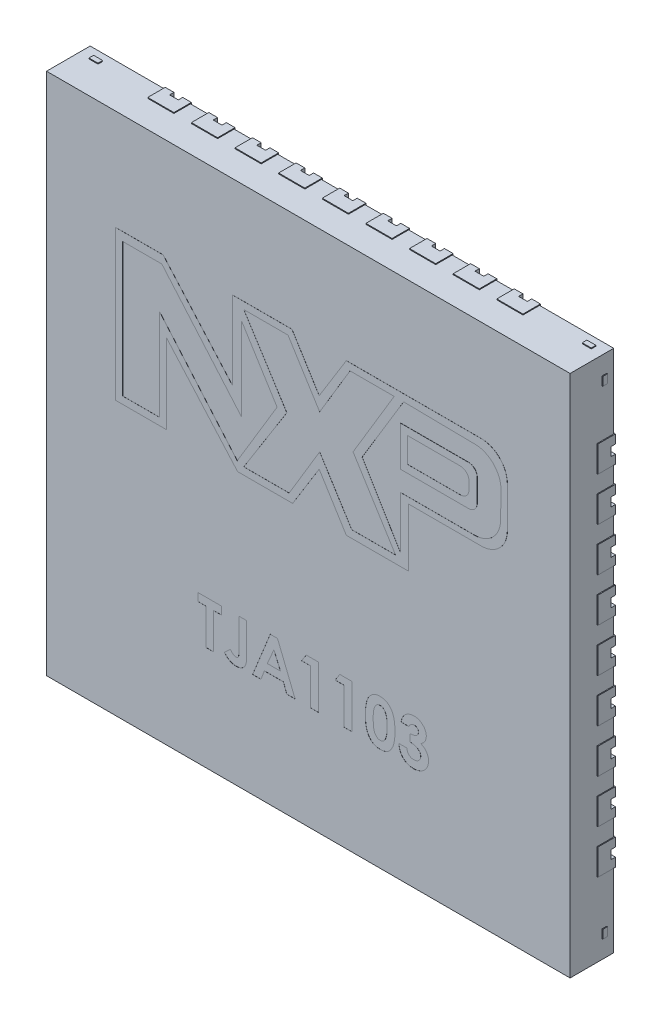
SolidWorks part; units mm, degrees
ref_plane "Front Plane" through (0, 0, 0) normal (0, 0, 1) x (1, 0, 0)
ref_plane "Top Plane" through (0, 0, 0) normal (0, 1, 0) x (1, 0, 0)
ref_plane "Right Plane" through (0, 0, 0) normal (1, 0, 0) x (0, 0, -1)
sketch "Sketch1" plane through (0, 0, 0) normal (0, 0, 1) x (1, 0, 0)
  line L1 (3, -3) -> (-3, -3)
  line L2 (3, -3) -> (3, 3)
  line L3 (3, 3) -> (-3, 3)
  line L4 (-3, -3) -> (-3, 3)
  line L5 (3, -3) -> (-3, 3) construction
  line L6 (3, 3) -> (-3, -3) construction
  point P0 (0, 0)
  dimension "D1" = 6
  dimension "D2" = 6
extrude "Boss-Extrude1" add sketch "Sketch1" along normal blind 0.5
sketch "Sketch3" plane through (0, 0, 0.5) normal (0, 0, 1) x (1, 0, 0)
  line L1 (-1.8824, 1.9808) -> (1.8824, 1.9808)
  line L2 (-1.8824, 1.9808) -> (-1.8824, -1.9808)
  line L3 (-1.8824, -1.9808) -> (1.8824, -1.9808)
  line L4 (1.8824, 1.9808) -> (1.8824, -1.9808)
  line L5 (-1.8824, 1.9808) -> (1.8824, -1.9808) construction
  line L6 (-1.8824, -1.9808) -> (1.8824, 1.9808) construction
  point P0 (0, 0)
sketch "Sketch4" plane through (0, 0, 0) normal (0, 0, -1) x (-1, 0, 0)
  line L0 (1.8824, 1.9808) -> (-1.8824, 1.9808) construction
  line L1 (-1.6324, 1.9808) -> (1.6324, 1.9808)
  line L2 (-1.8824, 1.7308) -> (-1.8824, -1.7308)
  line L3 (-1.6324, -1.9808) -> (1.6324, -1.9808)
  line L5 (-1.8824, 1.9808) -> (1.8824, -1.9808) construction
  line L6 (-1.8824, -1.9808) -> (1.8824, 1.9808) construction
  line L7 (-1.8824, 1.9808) -> (-1.8824, -1.9808) construction
  line L8 (1.8824, 1.7308) -> (1.8824, 1.4732)
  line L9 (1.8824, 1.9808) -> (1.8824, -1.9808) construction
  line L10 (1.8824, 0.8432) -> (1.8824, -1.7308)
  arc A0 (1.6324, -1.9808) -> (1.8824, -1.7308) centre (1.6324, -1.7308) ccw
  arc A1 (-1.8824, -1.7308) -> (-1.6324, -1.9808) centre (-1.6324, -1.7308) ccw
  arc A2 (1.6324, 1.9808) -> (1.8824, 1.7308) centre (1.6324, 1.7308) cw
  arc A3 (-1.6324, 1.9808) -> (-1.8824, 1.7308) centre (-1.6324, 1.7308) ccw
  arc A4 (1.8127, 1.3779) -> (1.8127, 0.9385) centre (1.8824, 1.1582) ccw
  arc A5 (1.8127, 0.9385) -> (1.8824, 0.8432) centre (1.7824, 0.8432) cw
  arc A6 (1.8824, 1.4732) -> (1.8127, 1.3779) centre (1.7824, 1.4732) cw
  point P0 (0, 0)
  point P29 (1.8824, 0.9277)
  point P32 (1.8824, 1.3887)
  dimension "D3" = 0.25
  dimension "D4" = 0.1
  dimension "D1" = 0
  dimension "D2" = 0
extrude "Cut-Extrude2" cut sketch "Sketch4" against normal blind 0.001
sketch "Sketch6" plane through (0, 0, 0.5) normal (0, 0, 1) x (1, 0, 0)
  line L0 (70.7212, 256.7277) -> (518.7212, 256.7277) construction
  line L1 (-2.2083, 0.1303) -> (-2.2083, 1.8455)
  line L2 (-2.2083, 1.8455) -> (-1.6631, 1.8455)
  line L3 (-1.6631, 1.8455) -> (-0.866, 0.9441)
  line L4 (-0.866, 0.9441) -> (-0.866, 1.8455)
  line L5 (-0.866, 1.8455) -> (-0.1867, 1.8455)
  line L6 (-0.1867, 1.8455) -> (0.1255, 1.3423)
  line L7 (0.1255, 1.3423) -> (0.4363, 1.8455)
  line L8 (0.4363, 1.8455) -> (1.9817, 1.8455)
  line L9 (2.2817, 1.5455) -> (2.2817, 1.0794)
  line L10 (1.9817, 0.7794) -> (1.148, 0.7794)
  line L11 (1.148, 0.7794) -> (1.148, 0.1127)
  line L12 (1.148, 0.1127) -> (0.4363, 0.1127)
  line L13 (0.4363, 0.1127) -> (0.1255, 0.6138)
  line L14 (0.1255, 0.6138) -> (-0.1785, 0.1216)
  line L15 (-0.1785, 0.1216) -> (-0.8093, 0.1216)
  line L16 (-0.8093, 0.1216) -> (-1.6263, 1.0454)
  line L17 (-1.6263, 1.0454) -> (-1.6263, 0.1303)
  line L18 (-1.6263, 0.1303) -> (-2.2083, 0.1303)
  line L19 (-2.1262, 0.213) -> (-2.1262, 1.7478)
  line L20 (-2.1262, 1.7478) -> (-1.6777, 1.7478)
  line L21 (-1.6777, 1.7478) -> (-0.7643, 0.6866)
  line L22 (-0.7643, 0.6866) -> (-0.7643, 1.6405)
  line L23 (-0.7643, 1.6405) -> (-0.3567, 0.9874)
  line L24 (-0.3567, 0.9874) -> (-0.8135, 0.2272)
  line L25 (-0.8135, 0.2272) -> (-1.7039, 1.2616)
  line L26 (-1.7039, 1.2616) -> (-1.7039, 0.213)
  line L27 (-1.7039, 0.213) -> (-2.1262, 0.213)
  line L28 (-0.739, 1.7656) -> (-0.2318, 1.7656)
  line L29 (-0.2318, 1.7656) -> (0.1309, 1.1851)
  line L30 (0.1309, 1.1851) -> (0.4789, 1.7656)
  line L31 (0.4789, 1.7656) -> (0.9852, 1.7656)
  line L32 (0.9852, 1.7656) -> (0.5138, 0.9793)
  line L33 (0.5138, 0.9793) -> (1.0013, 0.1991)
  line L34 (1.0013, 0.1991) -> (0.4983, 0.1991)
  line L35 (0.4983, 0.1991) -> (0.1309, 0.7872)
  line L36 (0.1309, 0.7872) -> (-0.2187, 0.2041)
  line L37 (-0.2187, 0.2041) -> (-0.739, 0.2041)
  line L38 (-0.739, 0.2041) -> (-0.2458, 0.9874)
  line L39 (-0.2458, 0.9874) -> (-0.739, 1.7656)
  line L40 (1.0935, 1.7656) -> (1.9132, 1.7541)
  line L41 (2.209, 1.4499) -> (2.2047, 1.1439)
  line L42 (1.9047, 0.8481) -> (1.0599, 0.8481)
  line L43 (1.0599, 0.8481) -> (1.0599, 0.2452)
  line L44 (1.0599, 0.2452) -> (0.6173, 0.9793)
  line L45 (0.6173, 0.9793) -> (1.0935, 1.7656)
  line L47 (1.0599, 1.5374) -> (1.8371, 1.5374)
  line L48 (1.9371, 1.4374) -> (1.9371, 1.1794)
  line L49 (1.8371, 1.0794) -> (1.0599, 1.0794)
  line L50 (1.0599, 1.5374) -> (1.0599, 1.0794)
  line L51 (1.1403, 1.4544) -> (1.7437, 1.4544)
  line L52 (1.1403, 1.4544) -> (1.1403, 1.1679)
  line L53 (1.1403, 1.1679) -> (1.7437, 1.1679)
  line L54 (1.8437, 1.3544) -> (1.8437, 1.2679)
  arc A0 (2.2817, 1.0794) -> (1.9817, 0.7794) centre (1.9817, 1.0794) cw
  arc A1 (1.9817, 1.8455) -> (2.2817, 1.5455) centre (1.9817, 1.5455) cw
  arc A2 (2.2047, 1.1439) -> (1.9047, 0.8481) centre (1.9047, 1.1481) cw
  arc A3 (1.9132, 1.7541) -> (2.209, 1.4499) centre (1.909, 1.4541) cw
  arc A4 (1.7437, 1.1679) -> (1.8437, 1.2679) centre (1.7437, 1.2679) ccw
  arc A5 (1.7437, 1.4544) -> (1.8437, 1.3544) centre (1.7437, 1.3544) cw
  arc A6 (1.9371, 1.1794) -> (1.8371, 1.0794) centre (1.8371, 1.1794) cw
  arc A7 (1.8371, 1.5374) -> (1.9371, 1.4374) centre (1.8371, 1.4374) cw
  dimension "D1" = 0.3
  dimension "D2" = 0.3
  dimension "D3" = 0.1
extrude "Boss-Extrude2" add sketch "Sketch6" along normal blind 0.001 contours A1 L8 L7 L6 L5 L4 L3 L2 L1 L18 L17 L16 L15 L14 L13 L12 L11 L10 A0 L9 L38 L39 L28 L29 L30 L31 L32 L33 L34 L35 L36 L37 L26 L27 L19 L20 L21 L22 L23 L24 L25 L40 A3 L41 A2 L42 L43 L44 | L52 L51 A5 L54 A4 L53 region at (-2.1602, 0.9879, 0.5)
sketch "Sketch8" plane through (0, 0, 0.5) normal (0, 0, 1) x (1, 0, 0)
  line L0 (-1.2697, -1.8064) -> (2.0877, -1.8064) construction
  text T0 "<b>TJA1103</b>" font "Century Gothic" height 0.5
  point P3 (-1.2346, -1.7332)
  point P4 (-1.5512, -1.7332)
  point P5 (-1.4079, -1.7332)
  point P6 (-1.2044, -1.7785)
  point P7 (0, 0)
  point P8 (-1.2697, -1.8064)
extrude "Cut-Extrude3" cut sketch "Sketch8" against normal blind 0.001
sketch "Sketch2" plane through (0, 0, 0) normal (0, 0, -1) x (-1, 0, 0)
  line L0 (-2, 2.65) -> (-2, 3.35) construction
  line L1 (-2.15, 2.65) -> (-2.15, 3.35)
  line L2 (-1.85, 2.65) -> (-1.85, 3.35)
  line L3 (-1.35, 2.65) -> (-1.35, 3.35)
  line L6 (-3, 3) -> (3, 3) construction
  line L7 (-1.65, 2.65) -> (-1.65, 3.35)
  line L8 (-1.5, 2.65) -> (-1.5, 3.35) construction
  line L9 (-0.85, 2.65) -> (-0.85, 3.35)
  line L10 (-1.15, 2.65) -> (-1.15, 3.35)
  line L11 (-1, 2.65) -> (-1, 3.35) construction
  line L12 (-0.35, 2.65) -> (-0.35, 3.35)
  line L13 (-0.65, 2.65) -> (-0.65, 3.35)
  line L14 (-0.5, 2.65) -> (-0.5, 3.35) construction
  line L15 (0.15, 2.65) -> (0.15, 3.35)
  line L16 (-0.15, 2.65) -> (-0.15, 3.35)
  line L17 (0, 2.65) -> (0, 3.35) construction
  line L18 (0.65, 2.65) -> (0.65, 3.35)
  line L19 (0.35, 2.65) -> (0.35, 3.35)
  line L20 (0.5, 2.65) -> (0.5, 3.35) construction
  line L21 (1.15, 2.65) -> (1.15, 3.35)
  line L22 (0.85, 2.65) -> (0.85, 3.35)
  line L23 (1, 2.65) -> (1, 3.35) construction
  line L24 (1.65, 2.65) -> (1.65, 3.35)
  line L25 (1.35, 2.65) -> (1.35, 3.35)
  line L26 (1.5, 2.65) -> (1.5, 3.35) construction
  line L27 (2.15, 2.65) -> (2.15, 3.35)
  line L28 (1.85, 2.65) -> (1.85, 3.35)
  line L29 (2, 2.65) -> (2, 3.35) construction
  line L30 (0, 0) -> (0, -1.6259) construction
  line L31 (0, 0) -> (1.65, 0) construction
  line L32 (-2, -2.65) -> (-2, -3.35) construction
  line L33 (-2.15, -2.65) -> (-2.15, -3.35)
  line L34 (-1.85, -2.65) -> (-1.85, -3.35)
  line L35 (-1.5, -2.65) -> (-1.5, -3.35) construction
  line L36 (-1.65, -2.65) -> (-1.65, -3.35)
  line L37 (-1.35, -2.65) -> (-1.35, -3.35)
  line L38 (-1, -2.65) -> (-1, -3.35) construction
  line L39 (-1.15, -2.65) -> (-1.15, -3.35)
  line L40 (-0.85, -2.65) -> (-0.85, -3.35)
  line L41 (-0.5, -2.65) -> (-0.5, -3.35) construction
  line L42 (-0.65, -2.65) -> (-0.65, -3.35)
  line L43 (-0.35, -2.65) -> (-0.35, -3.35)
  line L44 (0, -2.65) -> (0, -3.35) construction
  line L45 (-0.15, -2.65) -> (-0.15, -3.35)
  line L46 (0.15, -2.65) -> (0.15, -3.35)
  line L47 (0.5, -2.65) -> (0.5, -3.35) construction
  line L48 (0.35, -2.65) -> (0.35, -3.35)
  line L49 (0.65, -2.65) -> (0.65, -3.35)
  line L50 (1, -2.65) -> (1, -3.35) construction
  line L51 (0.85, -2.65) -> (0.85, -3.35)
  line L52 (1.15, -2.65) -> (1.15, -3.35)
  line L53 (1.5, -2.65) -> (1.5, -3.35) construction
  line L54 (1.35, -2.65) -> (1.35, -3.35)
  line L55 (1.65, -2.65) -> (1.65, -3.35)
  line L56 (2, -2.65) -> (2, -3.35) construction
  line L57 (1.85, -2.65) -> (1.85, -3.35)
  line L58 (2.15, -2.65) -> (2.15, -3.35)
  line L59 (2.65, 2) -> (3.35, 2) construction
  line L61 (-2.65, 2) -> (-3.35, 2) construction
  line L62 (-2.65, 2.15) -> (-3.35, 2.15)
  line L63 (-2.65, 1.85) -> (-3.35, 1.85)
  line L64 (-2.65, 1.5) -> (-3.35, 1.5) construction
  line L65 (-2.65, 1.65) -> (-3.35, 1.65)
  line L66 (-2.65, 1.35) -> (-3.35, 1.35)
  line L67 (-2.65, 1) -> (-3.35, 1) construction
  line L68 (-2.65, 1.15) -> (-3.35, 1.15)
  line L69 (-2.65, 0.85) -> (-3.35, 0.85)
  line L70 (-2.65, 0.5) -> (-3.35, 0.5) construction
  line L71 (-2.65, 0.65) -> (-3.35, 0.65)
  line L72 (-2.65, 0.35) -> (-3.35, 0.35)
  line L73 (-2.65, 0) -> (-3.35, 0) construction
  line L74 (-2.65, 0.15) -> (-3.35, 0.15)
  line L75 (-2.65, -0.15) -> (-3.35, -0.15)
  line L76 (-2.65, -0.5) -> (-3.35, -0.5) construction
  line L77 (-2.65, -0.35) -> (-3.35, -0.35)
  line L78 (-2.65, -0.65) -> (-3.35, -0.65)
  line L79 (-2.65, -1) -> (-3.35, -1) construction
  line L80 (-2.65, -0.85) -> (-3.35, -0.85)
  line L81 (-2.65, -1.15) -> (-3.35, -1.15)
  line L82 (-2.65, -1.5) -> (-3.35, -1.5) construction
  line L83 (-2.65, -1.35) -> (-3.35, -1.35)
  line L84 (-2.65, -1.65) -> (-3.35, -1.65)
  line L85 (-2.65, -2) -> (-3.35, -2) construction
  line L86 (-2.65, -1.85) -> (-3.35, -1.85)
  line L87 (-2.65, -2.15) -> (-3.35, -2.15)
  line L88 (2.65, 2.15) -> (3.35, 2.15)
  line L89 (2.65, 1.85) -> (3.35, 1.85)
  line L90 (2.65, 1.5) -> (3.35, 1.5) construction
  line L91 (2.65, 1.65) -> (3.35, 1.65)
  line L92 (2.65, 1.35) -> (3.35, 1.35)
  line L93 (2.65, 1) -> (3.35, 1) construction
  line L94 (2.65, 1.15) -> (3.35, 1.15)
  line L95 (2.65, 0.85) -> (3.35, 0.85)
  line L96 (2.65, 0.5) -> (3.35, 0.5) construction
  line L97 (2.65, 0.65) -> (3.35, 0.65)
  line L98 (2.65, 0.35) -> (3.35, 0.35)
  line L99 (2.65, 0) -> (3.35, 0) construction
  line L100 (2.65, 0.15) -> (3.35, 0.15)
  line L101 (2.65, -0.15) -> (3.35, -0.15)
  line L102 (2.65, -0.5) -> (3.35, -0.5) construction
  line L103 (2.65, -0.35) -> (3.35, -0.35)
  line L104 (2.65, -0.65) -> (3.35, -0.65)
  line L105 (2.65, -1) -> (3.35, -1) construction
  line L106 (2.65, -0.85) -> (3.35, -0.85)
  line L107 (2.65, -1.15) -> (3.35, -1.15)
  line L108 (2.65, -1.5) -> (3.35, -1.5) construction
  line L109 (2.65, -1.35) -> (3.35, -1.35)
  line L110 (2.65, -1.65) -> (3.35, -1.65)
  line L111 (2.65, -2) -> (3.35, -2) construction
  line L112 (2.65, -1.85) -> (3.35, -1.85)
  line L113 (2.65, -2.15) -> (3.35, -2.15)
  arc A0 (-2.15, 2.65) -> (-1.85, 2.65) centre (-2, 2.65) ccw
  arc A1 (-1.85, 3.35) -> (-2.15, 3.35) centre (-2, 3.35) ccw
  arc A4 (-1.65, 2.65) -> (-1.35, 2.65) centre (-1.5, 2.65) ccw
  arc A5 (-1.35, 3.35) -> (-1.65, 3.35) centre (-1.5, 3.35) ccw
  arc A6 (-1.15, 2.65) -> (-0.85, 2.65) centre (-1, 2.65) ccw
  arc A7 (-0.85, 3.35) -> (-1.15, 3.35) centre (-1, 3.35) ccw
  arc A8 (-0.65, 2.65) -> (-0.35, 2.65) centre (-0.5, 2.65) ccw
  arc A9 (-0.35, 3.35) -> (-0.65, 3.35) centre (-0.5, 3.35) ccw
  arc A10 (-0.15, 2.65) -> (0.15, 2.65) centre (0, 2.65) ccw
  arc A11 (0.15, 3.35) -> (-0.15, 3.35) centre (0, 3.35) ccw
  arc A12 (0.35, 2.65) -> (0.65, 2.65) centre (0.5, 2.65) ccw
  arc A13 (0.65, 3.35) -> (0.35, 3.35) centre (0.5, 3.35) ccw
  arc A14 (0.85, 2.65) -> (1.15, 2.65) centre (1, 2.65) ccw
  arc A15 (1.15, 3.35) -> (0.85, 3.35) centre (1, 3.35) ccw
  arc A16 (1.35, 2.65) -> (1.65, 2.65) centre (1.5, 2.65) ccw
  arc A17 (1.65, 3.35) -> (1.35, 3.35) centre (1.5, 3.35) ccw
  arc A18 (1.85, 2.65) -> (2.15, 2.65) centre (2, 2.65) ccw
  arc A19 (2.15, 3.35) -> (1.85, 3.35) centre (2, 3.35) ccw
  arc A20 (-2.15, -2.65) -> (-1.85, -2.65) centre (-2, -2.65) cw
  arc A21 (-1.85, -3.35) -> (-2.15, -3.35) centre (-2, -3.35) cw
  arc A22 (-1.65, -2.65) -> (-1.35, -2.65) centre (-1.5, -2.65) cw
  arc A23 (-1.35, -3.35) -> (-1.65, -3.35) centre (-1.5, -3.35) cw
  arc A24 (-1.15, -2.65) -> (-0.85, -2.65) centre (-1, -2.65) cw
  arc A25 (-0.85, -3.35) -> (-1.15, -3.35) centre (-1, -3.35) cw
  arc A26 (-0.65, -2.65) -> (-0.35, -2.65) centre (-0.5, -2.65) cw
  arc A27 (-0.35, -3.35) -> (-0.65, -3.35) centre (-0.5, -3.35) cw
  arc A28 (-0.15, -2.65) -> (0.15, -2.65) centre (0, -2.65) cw
  arc A29 (0.15, -3.35) -> (-0.15, -3.35) centre (0, -3.35) cw
  arc A30 (0.35, -2.65) -> (0.65, -2.65) centre (0.5, -2.65) cw
  arc A31 (0.65, -3.35) -> (0.35, -3.35) centre (0.5, -3.35) cw
  arc A32 (0.85, -2.65) -> (1.15, -2.65) centre (1, -2.65) cw
  arc A33 (1.15, -3.35) -> (0.85, -3.35) centre (1, -3.35) cw
  arc A34 (1.35, -2.65) -> (1.65, -2.65) centre (1.5, -2.65) cw
  arc A35 (1.65, -3.35) -> (1.35, -3.35) centre (1.5, -3.35) cw
  arc A36 (1.85, -2.65) -> (2.15, -2.65) centre (2, -2.65) cw
  arc A37 (2.15, -3.35) -> (1.85, -3.35) centre (2, -3.35) cw
  arc A38 (-2.65, 2.15) -> (-2.65, 1.85) centre (-2.65, 2) cw
  arc A39 (-3.35, 1.85) -> (-3.35, 2.15) centre (-3.35, 2) cw
  arc A40 (-2.65, 1.65) -> (-2.65, 1.35) centre (-2.65, 1.5) cw
  arc A41 (-3.35, 1.35) -> (-3.35, 1.65) centre (-3.35, 1.5) cw
  arc A42 (-2.65, 1.15) -> (-2.65, 0.85) centre (-2.65, 1) cw
  arc A43 (-3.35, 0.85) -> (-3.35, 1.15) centre (-3.35, 1) cw
  arc A44 (-2.65, 0.65) -> (-2.65, 0.35) centre (-2.65, 0.5) cw
  arc A45 (-3.35, 0.35) -> (-3.35, 0.65) centre (-3.35, 0.5) cw
  arc A46 (-2.65, 0.15) -> (-2.65, -0.15) centre (-2.65, 0) cw
  arc A47 (-3.35, -0.15) -> (-3.35, 0.15) centre (-3.35, 0) cw
  arc A48 (-2.65, -0.35) -> (-2.65, -0.65) centre (-2.65, -0.5) cw
  arc A49 (-3.35, -0.65) -> (-3.35, -0.35) centre (-3.35, -0.5) cw
  arc A50 (-2.65, -0.85) -> (-2.65, -1.15) centre (-2.65, -1) cw
  arc A51 (-3.35, -1.15) -> (-3.35, -0.85) centre (-3.35, -1) cw
  arc A52 (-2.65, -1.35) -> (-2.65, -1.65) centre (-2.65, -1.5) cw
  arc A53 (-3.35, -1.65) -> (-3.35, -1.35) centre (-3.35, -1.5) cw
  arc A54 (-2.65, -1.85) -> (-2.65, -2.15) centre (-2.65, -2) cw
  arc A55 (-3.35, -2.15) -> (-3.35, -1.85) centre (-3.35, -2) cw
  arc A56 (2.65, 2.15) -> (2.65, 1.85) centre (2.65, 2) ccw
  arc A57 (3.35, 1.85) -> (3.35, 2.15) centre (3.35, 2) ccw
  arc A58 (2.65, 1.65) -> (2.65, 1.35) centre (2.65, 1.5) ccw
  arc A59 (3.35, 1.35) -> (3.35, 1.65) centre (3.35, 1.5) ccw
  arc A60 (2.65, 1.15) -> (2.65, 0.85) centre (2.65, 1) ccw
  arc A61 (3.35, 0.85) -> (3.35, 1.15) centre (3.35, 1) ccw
  arc A62 (2.65, 0.65) -> (2.65, 0.35) centre (2.65, 0.5) ccw
  arc A63 (3.35, 0.35) -> (3.35, 0.65) centre (3.35, 0.5) ccw
  arc A64 (2.65, 0.15) -> (2.65, -0.15) centre (2.65, 0) ccw
  arc A65 (3.35, -0.15) -> (3.35, 0.15) centre (3.35, 0) ccw
  arc A66 (2.65, -0.35) -> (2.65, -0.65) centre (2.65, -0.5) ccw
  arc A67 (3.35, -0.65) -> (3.35, -0.35) centre (3.35, -0.5) ccw
  arc A68 (2.65, -0.85) -> (2.65, -1.15) centre (2.65, -1) ccw
  arc A69 (3.35, -1.15) -> (3.35, -0.85) centre (3.35, -1) ccw
  arc A70 (2.65, -1.35) -> (2.65, -1.65) centre (2.65, -1.5) ccw
  arc A71 (3.35, -1.65) -> (3.35, -1.35) centre (3.35, -1.5) ccw
  arc A72 (2.65, -1.85) -> (2.65, -2.15) centre (2.65, -2) ccw
  arc A73 (3.35, -2.15) -> (3.35, -1.85) centre (3.35, -2) ccw
  point P2 (-2, 3)
  point P10 (-1.5, 3)
  point P16 (-2, 2.5)
  point P21 (-1, 3)
  point P28 (-0.5, 3)
  point P35 (0, 3)
  point P42 (0.5, 3)
  point P49 (1, 3)
  point P56 (1.5, 3)
  point P63 (2, 3)
  point P72 (-2, -3)
  point P79 (-1.5, -3)
  point P86 (-1, -3)
  point P93 (-0.5, -3)
  point P100 (0, -3)
  point P107 (0.5, -3)
  point P114 (1, -3)
  point P121 (1.5, -3)
  point P128 (2, -3)
  point P136 (3, 2)
  point P140 (-3, 2)
  point P147 (-3, 1.5)
  point P154 (-3, 1)
  point P161 (-3, 0.5)
  point P168 (-3, 0)
  point P175 (-3, -0.5)
  point P182 (-3, -1)
  point P189 (-3, -1.5)
  point P196 (-3, -2)
  point P206 (3, 1.5)
  point P213 (3, 1)
  point P220 (3, 0.5)
  point P227 (3, 0)
  point P234 (3, -0.5)
  point P241 (3, -1)
  point P248 (3, -1.5)
  point P255 (3, -2)
  dimension "D1" = 0.3
  dimension "D2" = 9
  dimension "D4" = 0
  dimension "D5" = 0.5
  dimension "D8" = 2
sketch "Sketch10" plane through (0, 0, 0.5) normal (0, 0, 1) x (1, 0, 0)
  line L0 (1.0599, 1.5374) -> (1.8371, 1.5374)
  line L1 (1.0599, 1.5374) -> (1.0599, 1.0794)
  line L2 (1.0599, 1.0794) -> (1.8371, 1.0794)
  line L3 (1.9371, 1.4374) -> (1.9371, 1.1794)
  line L4 (1.8437, 1.3544) -> (1.8437, 1.2679)
  line L5 (1.7437, 1.4544) -> (1.1403, 1.4544)
  line L6 (1.1403, 1.4544) -> (1.1403, 1.1679)
  line L7 (1.1403, 1.1679) -> (1.7437, 1.1679)
  line L8 (1.1403, 1.4544) -> (1.7437, 1.4544) construction
  line L9 (1.1403, 1.4544) -> (1.1403, 1.1679) construction
  arc A0 (1.8371, 1.5374) -> (1.9371, 1.4374) centre (1.8371, 1.4374) cw
  arc A1 (1.9371, 1.1794) -> (1.8371, 1.0794) centre (1.8371, 1.1794) cw
  arc A2 (1.8437, 1.2679) -> (1.7437, 1.1679) centre (1.7437, 1.2679) cw
  arc A3 (1.7437, 1.4544) -> (1.8437, 1.3544) centre (1.7437, 1.3544) cw
  point P26 (1.0409, 1.4852)
extrude "Boss-Extrude3" add sketch "Sketch10" along normal blind 0.002
extrude "Boss-Extrude4" add sketch "Sketch2" along normal blind 0.01
sketch "Sketch11" plane through (0, 0, 0.5) normal (0, 0, 1) x (1, 0, 0)
  line L1 (-3, 3) -> (3, 3)
  line L2 (-3, 3) -> (-3, -3)
  line L3 (-3, -3) -> (3, -3)
  line L4 (3, 3) -> (3, -3)
  line L5 (-4.69, 4.3097) -> (4.6689, 4.3097)
  line L6 (-4.69, 4.3097) -> (-4.69, -5.1125)
  line L7 (-4.69, -5.1125) -> (4.6689, -5.1125)
  line L8 (4.6689, 4.3097) -> (4.6689, -5.1125)
extrude "Cut-Extrude4" cut sketch "Sketch11" against normal blind 10.01
sketch "Sketch12" plane through (0, 0, -0.01) normal (0, 0, -1) x (-1, 0, 0)
  line L0 (-3, 3) -> (-1.6807, 1.6807) construction
  line L1 (-3, 3) -> (-2.15, 3) construction
  line L2 (0, 0) -> (0.5, 0) construction
  line L3 (0, 0) -> (0, 0.8589) construction
  circle A0 centre (-2, 2.65) radius 0.025
  circle A1 centre (-1.5, 2.65) radius 0.025
  circle A2 centre (-1, 2.65) radius 0.025
  circle A3 centre (-0.5, 2.65) radius 0.025
  circle A4 centre (0, 2.65) radius 0.025
  circle A5 centre (0.5, 2.65) radius 0.025
  circle A6 centre (1, 2.65) radius 0.025
  circle A7 centre (1.5, 2.65) radius 0.025
  circle A8 centre (2, 2.65) radius 0.025
  circle A9 centre (-2.65, -2) radius 0.025
  circle A10 centre (-2.65, -1.5) radius 0.025
  circle A11 centre (-2.65, -1) radius 0.025
  circle A12 centre (-2.65, -0.5) radius 0.025
  circle A13 centre (-2.65, 0) radius 0.025
  circle A14 centre (-2.65, 0.5) radius 0.025
  circle A15 centre (-2.65, 1) radius 0.025
  circle A16 centre (-2.65, 1.5) radius 0.025
  circle A17 centre (-2.65, 2) radius 0.025
  circle A18 centre (2, -2.65) radius 0.025
  circle A19 centre (1.5, -2.65) radius 0.025
  circle A20 centre (1, -2.65) radius 0.025
  circle A21 centre (0.5, -2.65) radius 0.025
  circle A22 centre (0, -2.65) radius 0.025
  circle A23 centre (-0.5, -2.65) radius 0.025
  circle A24 centre (-1, -2.65) radius 0.025
  circle A25 centre (-1.5, -2.65) radius 0.025
  circle A26 centre (-2, -2.65) radius 0.025
  circle A27 centre (2.65, 2) radius 0.025
  circle A28 centre (2.65, 1.5) radius 0.025
  circle A29 centre (2.65, 1) radius 0.025
  circle A30 centre (2.65, 0.5) radius 0.025
  circle A31 centre (2.65, 0) radius 0.025
  circle A32 centre (2.65, -0.5) radius 0.025
  circle A33 centre (2.65, -1) radius 0.025
  circle A34 centre (2.65, -1.5) radius 0.025
  circle A35 centre (2.65, -2) radius 0.025
  dimension "D1" = 0.05
  dimension "D3" = 45
  dimension "D2" = 9
sketch "Sketch14" plane through (0, -3, 0) normal (0, -1, 0) x (1, 0, 0)
  line L0 (-1.85, -0.01) -> (-1.85, 0) construction
  line L1 (-2.15, -0.01) -> (-1.85, -0.01)
  line L2 (-2.15, -0.01) -> (-2.15, 0.19)
  line L3 (-2.15, 0.19) -> (-1.85, 0.19)
  line L4 (-1.85, -0.01) -> (-1.85, 0.19)
  line L5 (-1.65, -0.01) -> (-1.65, 0.19)
  line L6 (-1.65, -0.01) -> (-1.35, -0.01)
  line L7 (-1.35, -0.01) -> (-1.35, 0.19)
  line L8 (-1.65, 0.19) -> (-1.35, 0.19)
  line L9 (-1.15, -0.01) -> (-1.15, 0.19)
  line L10 (-1.15, -0.01) -> (-0.85, -0.01)
  line L11 (-0.85, -0.01) -> (-0.85, 0.19)
  line L12 (-1.15, 0.19) -> (-0.85, 0.19)
  line L13 (-0.65, -0.01) -> (-0.65, 0.19)
  line L14 (-0.65, -0.01) -> (-0.35, -0.01)
  line L15 (-0.35, -0.01) -> (-0.35, 0.19)
  line L16 (-0.65, 0.19) -> (-0.35, 0.19)
  line L17 (-0.15, -0.01) -> (-0.15, 0.19)
  line L18 (-0.15, -0.01) -> (0.15, -0.01)
  line L19 (0.15, -0.01) -> (0.15, 0.19)
  line L20 (-0.15, 0.19) -> (0.15, 0.19)
  line L21 (0.35, -0.01) -> (0.35, 0.19)
  line L22 (0.35, -0.01) -> (0.65, -0.01)
  line L23 (0.65, -0.01) -> (0.65, 0.19)
  line L24 (0.35, 0.19) -> (0.65, 0.19)
  line L25 (0.85, -0.01) -> (0.85, 0.19)
  line L26 (0.85, -0.01) -> (1.15, -0.01)
  line L27 (1.15, -0.01) -> (1.15, 0.19)
  line L28 (0.85, 0.19) -> (1.15, 0.19)
  line L29 (1.35, -0.01) -> (1.35, 0.19)
  line L30 (1.35, -0.01) -> (1.65, -0.01)
  line L31 (1.65, -0.01) -> (1.65, 0.19)
  line L32 (1.35, 0.19) -> (1.65, 0.19)
  line L33 (1.85, -0.01) -> (1.85, 0.19)
  line L34 (1.85, -0.01) -> (2.15, -0.01)
  line L35 (2.15, -0.01) -> (2.15, 0.19)
  line L36 (1.85, 0.19) -> (2.15, 0.19)
  dimension "D1" = 0
  dimension "D2" = 0.2
  dimension "D3" = 9
extrude "Boss-Extrude5" add sketch "Sketch14" along normal blind 0.01
sketch "Sketch15" plane through (-3, 0, 0) normal (-1, 0, 0) x (0, 0, 1)
  line L0 (-0.01, -1.65) -> (-0.01, -1.35)
  line L1 (-0.01, -2.15) -> (0.19, -2.15)
  line L2 (-0.01, -2.15) -> (-0.01, -1.85)
  line L3 (-0.01, -1.85) -> (0.19, -1.85)
  line L4 (0.19, -2.15) -> (0.19, -1.85)
  line L5 (-0.01, -1.65) -> (0.19, -1.65)
  line L6 (0.19, -1.65) -> (0.19, -1.35)
  line L7 (-0.01, -1.35) -> (0.19, -1.35)
  line L8 (-0.01, -1.15) -> (-0.01, -0.85)
  line L9 (-0.01, -1.15) -> (0.19, -1.15)
  line L10 (0.19, -1.15) -> (0.19, -0.85)
  line L11 (-0.01, -0.85) -> (0.19, -0.85)
  line L12 (-0.01, -0.65) -> (-0.01, -0.35)
  line L13 (-0.01, -0.65) -> (0.19, -0.65)
  line L14 (0.19, -0.65) -> (0.19, -0.35)
  line L15 (-0.01, -0.35) -> (0.19, -0.35)
  line L16 (-0.01, -0.15) -> (-0.01, 0.15)
  line L17 (-0.01, -0.15) -> (0.19, -0.15)
  line L18 (0.19, -0.15) -> (0.19, 0.15)
  line L19 (-0.01, 0.15) -> (0.19, 0.15)
  line L20 (-0.01, 0.35) -> (-0.01, 0.65)
  line L21 (-0.01, 0.35) -> (0.19, 0.35)
  line L22 (0.19, 0.35) -> (0.19, 0.65)
  line L23 (-0.01, 0.65) -> (0.19, 0.65)
  line L24 (-0.01, 0.85) -> (-0.01, 1.15)
  line L25 (-0.01, 0.85) -> (0.19, 0.85)
  line L26 (0.19, 0.85) -> (0.19, 1.15)
  line L27 (-0.01, 1.15) -> (0.19, 1.15)
  line L28 (-0.01, 1.35) -> (-0.01, 1.65)
  line L29 (-0.01, 1.35) -> (0.19, 1.35)
  line L30 (0.19, 1.35) -> (0.19, 1.65)
  line L31 (-0.01, 1.65) -> (0.19, 1.65)
  line L32 (-0.01, 1.85) -> (-0.01, 2.15)
  line L33 (-0.01, 1.85) -> (0.19, 1.85)
  line L34 (0.19, 1.85) -> (0.19, 2.15)
  line L35 (-0.01, 2.15) -> (0.19, 2.15)
  dimension "D1" = 0
  dimension "D2" = 0.2
  dimension "D3" = 9
extrude "Boss-Extrude6" add sketch "Sketch15" along normal blind 0.01
mirror "Mirror1" about plane through (0, 0, 0) normal (1, 0, 0) of "Boss-Extrude6"
mirror "Mirror2" about plane through (0, 0, 0) normal (0, 1, 0) of "Boss-Extrude5"
sketch "Sketch16" plane through (0, 0, -0.01) normal (0, 0, -1) x (-1, 0, 0)
  line L0 (-2, 3.06) -> (-2, 2.96) construction
  line L1 (-1.85, 3.01) -> (-2.15, 3.01) construction
  line L2 (-1.95, 3.06) -> (-1.95, 2.96)
  line L3 (-2.05, 3.06) -> (-2.05, 2.96)
  line L4 (-1.55, 3.06) -> (-1.55, 2.96)
  line L5 (-1.45, 3.06) -> (-1.45, 2.96)
  line L6 (-1.5, 3.06) -> (-1.5, 2.96) construction
  line L7 (-1.05, 3.06) -> (-1.05, 2.96)
  line L8 (-0.95, 3.06) -> (-0.95, 2.96)
  line L9 (-1, 3.06) -> (-1, 2.96) construction
  line L10 (-0.55, 3.06) -> (-0.55, 2.96)
  line L11 (-0.45, 3.06) -> (-0.45, 2.96)
  line L12 (-0.5, 3.06) -> (-0.5, 2.96) construction
  line L13 (-0.05, 3.06) -> (-0.05, 2.96)
  line L14 (0.05, 3.06) -> (0.05, 2.96)
  line L15 (0, 3.06) -> (0, 2.96) construction
  line L16 (0.45, 3.06) -> (0.45, 2.96)
  line L17 (0.55, 3.06) -> (0.55, 2.96)
  line L18 (0.5, 3.06) -> (0.5, 2.96) construction
  line L19 (0.95, 3.06) -> (0.95, 2.96)
  line L20 (1.05, 3.06) -> (1.05, 2.96)
  line L21 (1, 3.06) -> (1, 2.96) construction
  line L22 (1.45, 3.06) -> (1.45, 2.96)
  line L23 (1.55, 3.06) -> (1.55, 2.96)
  line L24 (1.5, 3.06) -> (1.5, 2.96) construction
  line L25 (1.95, 3.06) -> (1.95, 2.96)
  line L26 (2.05, 3.06) -> (2.05, 2.96)
  line L27 (2, 3.06) -> (2, 2.96) construction
  line L28 (0, 0) -> (0.7795, 0) construction
  line L29 (0, 0) -> (0, 0.8504) construction
  line L30 (-2, -3.06) -> (-2, -2.96) construction
  line L31 (-1.95, -3.06) -> (-1.95, -2.96)
  line L32 (-2.05, -3.06) -> (-2.05, -2.96)
  line L33 (-1.5, -3.06) -> (-1.5, -2.96) construction
  line L34 (-1.45, -3.06) -> (-1.45, -2.96)
  line L35 (-1.55, -3.06) -> (-1.55, -2.96)
  line L36 (-1, -3.06) -> (-1, -2.96) construction
  line L37 (-0.95, -3.06) -> (-0.95, -2.96)
  line L38 (-1.05, -3.06) -> (-1.05, -2.96)
  line L39 (-0.5, -3.06) -> (-0.5, -2.96) construction
  line L40 (-0.45, -3.06) -> (-0.45, -2.96)
  line L41 (-0.55, -3.06) -> (-0.55, -2.96)
  line L42 (0, -3.06) -> (0, -2.96) construction
  line L43 (0.05, -3.06) -> (0.05, -2.96)
  line L44 (-0.05, -3.06) -> (-0.05, -2.96)
  line L45 (0.5, -3.06) -> (0.5, -2.96) construction
  line L46 (0.55, -3.06) -> (0.55, -2.96)
  line L47 (0.45, -3.06) -> (0.45, -2.96)
  line L48 (1, -3.06) -> (1, -2.96) construction
  line L49 (1.05, -3.06) -> (1.05, -2.96)
  line L50 (0.95, -3.06) -> (0.95, -2.96)
  line L51 (1.5, -3.06) -> (1.5, -2.96) construction
  line L52 (1.55, -3.06) -> (1.55, -2.96)
  line L53 (1.45, -3.06) -> (1.45, -2.96)
  line L54 (2, -3.06) -> (2, -2.96) construction
  line L55 (2.05, -3.06) -> (2.05, -2.96)
  line L56 (1.95, -3.06) -> (1.95, -2.96)
  line L57 (-3.06, 2) -> (-2.96, 2) construction
  line L58 (-3.01, 2.15) -> (-3.01, 1.85) construction
  line L59 (-3.06, 2.05) -> (-2.96, 2.05)
  line L60 (-3.06, 1.95) -> (-2.96, 1.95)
  line L61 (-3.06, 1.45) -> (-2.96, 1.45)
  line L62 (-3.06, 1.55) -> (-2.96, 1.55)
  line L63 (-3.06, 1.5) -> (-2.96, 1.5) construction
  line L64 (-3.06, 0.95) -> (-2.96, 0.95)
  line L65 (-3.06, 1.05) -> (-2.96, 1.05)
  line L66 (-3.06, 1) -> (-2.96, 1) construction
  line L67 (-3.06, 0.45) -> (-2.96, 0.45)
  line L68 (-3.06, 0.55) -> (-2.96, 0.55)
  line L69 (-3.06, 0.5) -> (-2.96, 0.5) construction
  line L70 (-3.06, -0.05) -> (-2.96, -0.05)
  line L71 (-3.06, 0.05) -> (-2.96, 0.05)
  line L72 (-3.06, 0) -> (-2.96, 0) construction
  line L73 (-3.06, -0.55) -> (-2.96, -0.55)
  line L74 (-3.06, -0.45) -> (-2.96, -0.45)
  line L75 (-3.06, -0.5) -> (-2.96, -0.5) construction
  line L76 (-3.06, -1.05) -> (-2.96, -1.05)
  line L77 (-3.06, -0.95) -> (-2.96, -0.95)
  line L78 (-3.06, -1) -> (-2.96, -1) construction
  line L79 (-3.06, -1.55) -> (-2.96, -1.55)
  line L80 (-3.06, -1.45) -> (-2.96, -1.45)
  line L81 (-3.06, -1.5) -> (-2.96, -1.5) construction
  line L82 (-3.06, -2.05) -> (-2.96, -2.05)
  line L83 (-3.06, -1.95) -> (-2.96, -1.95)
  line L84 (-3.06, -2) -> (-2.96, -2) construction
  line L85 (3.06, 2) -> (2.96, 2) construction
  line L86 (3.06, 2.05) -> (2.96, 2.05)
  line L87 (3.06, 1.95) -> (2.96, 1.95)
  line L88 (3.06, 1.5) -> (2.96, 1.5) construction
  line L89 (3.06, 1.55) -> (2.96, 1.55)
  line L90 (3.06, 1.45) -> (2.96, 1.45)
  line L91 (3.06, 1) -> (2.96, 1) construction
  line L92 (3.06, 1.05) -> (2.96, 1.05)
  line L93 (3.06, 0.95) -> (2.96, 0.95)
  line L94 (3.06, 0.5) -> (2.96, 0.5) construction
  line L95 (3.06, 0.55) -> (2.96, 0.55)
  line L96 (3.06, 0.45) -> (2.96, 0.45)
  line L97 (3.06, 0) -> (2.96, 0) construction
  line L98 (3.06, 0.05) -> (2.96, 0.05)
  line L99 (3.06, -0.05) -> (2.96, -0.05)
  line L100 (3.06, -0.5) -> (2.96, -0.5) construction
  line L101 (3.06, -0.45) -> (2.96, -0.45)
  line L102 (3.06, -0.55) -> (2.96, -0.55)
  line L103 (3.06, -1) -> (2.96, -1) construction
  line L104 (3.06, -0.95) -> (2.96, -0.95)
  line L105 (3.06, -1.05) -> (2.96, -1.05)
  line L106 (3.06, -1.5) -> (2.96, -1.5) construction
  line L107 (3.06, -1.45) -> (2.96, -1.45)
  line L108 (3.06, -1.55) -> (2.96, -1.55)
  line L109 (3.06, -2) -> (2.96, -2) construction
  line L110 (3.06, -1.95) -> (2.96, -1.95)
  line L111 (3.06, -2.05) -> (2.96, -2.05)
  arc A0 (-1.95, 3.06) -> (-2.05, 3.06) centre (-2, 3.06) ccw
  arc A1 (-2.05, 2.96) -> (-1.95, 2.96) centre (-2, 2.96) ccw
  arc A2 (-1.45, 3.06) -> (-1.55, 3.06) centre (-1.5, 3.06) ccw
  arc A3 (-1.55, 2.96) -> (-1.45, 2.96) centre (-1.5, 2.96) ccw
  arc A4 (-0.95, 3.06) -> (-1.05, 3.06) centre (-1, 3.06) ccw
  arc A5 (-1.05, 2.96) -> (-0.95, 2.96) centre (-1, 2.96) ccw
  arc A6 (-0.45, 3.06) -> (-0.55, 3.06) centre (-0.5, 3.06) ccw
  arc A7 (-0.55, 2.96) -> (-0.45, 2.96) centre (-0.5, 2.96) ccw
  arc A8 (0.05, 3.06) -> (-0.05, 3.06) centre (0, 3.06) ccw
  arc A9 (-0.05, 2.96) -> (0.05, 2.96) centre (0, 2.96) ccw
  arc A10 (0.55, 3.06) -> (0.45, 3.06) centre (0.5, 3.06) ccw
  arc A11 (0.45, 2.96) -> (0.55, 2.96) centre (0.5, 2.96) ccw
  arc A12 (1.05, 3.06) -> (0.95, 3.06) centre (1, 3.06) ccw
  arc A13 (0.95, 2.96) -> (1.05, 2.96) centre (1, 2.96) ccw
  arc A14 (1.55, 3.06) -> (1.45, 3.06) centre (1.5, 3.06) ccw
  arc A15 (1.45, 2.96) -> (1.55, 2.96) centre (1.5, 2.96) ccw
  arc A16 (2.05, 3.06) -> (1.95, 3.06) centre (2, 3.06) ccw
  arc A17 (1.95, 2.96) -> (2.05, 2.96) centre (2, 2.96) ccw
  arc A18 (-1.95, -3.06) -> (-2.05, -3.06) centre (-2, -3.06) cw
  arc A19 (-2.05, -2.96) -> (-1.95, -2.96) centre (-2, -2.96) cw
  arc A20 (-1.45, -3.06) -> (-1.55, -3.06) centre (-1.5, -3.06) cw
  arc A21 (-1.55, -2.96) -> (-1.45, -2.96) centre (-1.5, -2.96) cw
  arc A22 (-0.95, -3.06) -> (-1.05, -3.06) centre (-1, -3.06) cw
  arc A23 (-1.05, -2.96) -> (-0.95, -2.96) centre (-1, -2.96) cw
  arc A24 (-0.45, -3.06) -> (-0.55, -3.06) centre (-0.5, -3.06) cw
  arc A25 (-0.55, -2.96) -> (-0.45, -2.96) centre (-0.5, -2.96) cw
  arc A26 (0.05, -3.06) -> (-0.05, -3.06) centre (0, -3.06) cw
  arc A27 (-0.05, -2.96) -> (0.05, -2.96) centre (0, -2.96) cw
  arc A28 (0.55, -3.06) -> (0.45, -3.06) centre (0.5, -3.06) cw
  arc A29 (0.45, -2.96) -> (0.55, -2.96) centre (0.5, -2.96) cw
  arc A30 (1.05, -3.06) -> (0.95, -3.06) centre (1, -3.06) cw
  arc A31 (0.95, -2.96) -> (1.05, -2.96) centre (1, -2.96) cw
  arc A32 (1.55, -3.06) -> (1.45, -3.06) centre (1.5, -3.06) cw
  arc A33 (1.45, -2.96) -> (1.55, -2.96) centre (1.5, -2.96) cw
  arc A34 (2.05, -3.06) -> (1.95, -3.06) centre (2, -3.06) cw
  arc A35 (1.95, -2.96) -> (2.05, -2.96) centre (2, -2.96) cw
  arc A36 (-3.06, 2.05) -> (-3.06, 1.95) centre (-3.06, 2) ccw
  arc A37 (-2.96, 1.95) -> (-2.96, 2.05) centre (-2.96, 2) ccw
  arc A38 (-3.06, 1.55) -> (-3.06, 1.45) centre (-3.06, 1.5) ccw
  arc A39 (-2.96, 1.45) -> (-2.96, 1.55) centre (-2.96, 1.5) ccw
  arc A40 (-3.06, 1.05) -> (-3.06, 0.95) centre (-3.06, 1) ccw
  arc A41 (-2.96, 0.95) -> (-2.96, 1.05) centre (-2.96, 1) ccw
  arc A42 (-3.06, 0.55) -> (-3.06, 0.45) centre (-3.06, 0.5) ccw
  arc A43 (-2.96, 0.45) -> (-2.96, 0.55) centre (-2.96, 0.5) ccw
  arc A44 (-3.06, 0.05) -> (-3.06, -0.05) centre (-3.06, 0) ccw
  arc A45 (-2.96, -0.05) -> (-2.96, 0.05) centre (-2.96, 0) ccw
  arc A46 (-3.06, -0.45) -> (-3.06, -0.55) centre (-3.06, -0.5) ccw
  arc A47 (-2.96, -0.55) -> (-2.96, -0.45) centre (-2.96, -0.5) ccw
  arc A48 (-3.06, -0.95) -> (-3.06, -1.05) centre (-3.06, -1) ccw
  arc A49 (-2.96, -1.05) -> (-2.96, -0.95) centre (-2.96, -1) ccw
  arc A50 (-3.06, -1.45) -> (-3.06, -1.55) centre (-3.06, -1.5) ccw
  arc A51 (-2.96, -1.55) -> (-2.96, -1.45) centre (-2.96, -1.5) ccw
  arc A52 (-3.06, -1.95) -> (-3.06, -2.05) centre (-3.06, -2) ccw
  arc A53 (-2.96, -2.05) -> (-2.96, -1.95) centre (-2.96, -2) ccw
  arc A54 (3.06, 2.05) -> (3.06, 1.95) centre (3.06, 2) cw
  arc A55 (2.96, 1.95) -> (2.96, 2.05) centre (2.96, 2) cw
  arc A56 (3.06, 1.55) -> (3.06, 1.45) centre (3.06, 1.5) cw
  arc A57 (2.96, 1.45) -> (2.96, 1.55) centre (2.96, 1.5) cw
  arc A58 (3.06, 1.05) -> (3.06, 0.95) centre (3.06, 1) cw
  arc A59 (2.96, 0.95) -> (2.96, 1.05) centre (2.96, 1) cw
  arc A60 (3.06, 0.55) -> (3.06, 0.45) centre (3.06, 0.5) cw
  arc A61 (2.96, 0.45) -> (2.96, 0.55) centre (2.96, 0.5) cw
  arc A62 (3.06, 0.05) -> (3.06, -0.05) centre (3.06, 0) cw
  arc A63 (2.96, -0.05) -> (2.96, 0.05) centre (2.96, 0) cw
  arc A64 (3.06, -0.45) -> (3.06, -0.55) centre (3.06, -0.5) cw
  arc A65 (2.96, -0.55) -> (2.96, -0.45) centre (2.96, -0.5) cw
  arc A66 (3.06, -0.95) -> (3.06, -1.05) centre (3.06, -1) cw
  arc A67 (2.96, -1.05) -> (2.96, -0.95) centre (2.96, -1) cw
  arc A68 (3.06, -1.45) -> (3.06, -1.55) centre (3.06, -1.5) cw
  arc A69 (2.96, -1.55) -> (2.96, -1.45) centre (2.96, -1.5) cw
  arc A70 (3.06, -1.95) -> (3.06, -2.05) centre (3.06, -2) cw
  arc A71 (2.96, -2.05) -> (2.96, -1.95) centre (2.96, -2) cw
  point P4 (-2, 3.01)
  point P12 (-1.5, 3.01)
  point P19 (-1, 3.01)
  point P26 (-0.5, 3.01)
  point P33 (0, 3.01)
  point P40 (0.5, 3.01)
  point P47 (1, 3.01)
  point P54 (1.5, 3.01)
  point P61 (2, 3.01)
  point P71 (-2, -3.01)
  point P78 (-1.5, -3.01)
  point P85 (-1, -3.01)
  point P92 (-0.5, -3.01)
  point P99 (0, -3.01)
  point P106 (0.5, -3.01)
  point P113 (1, -3.01)
  point P120 (1.5, -3.01)
  point P127 (2, -3.01)
  point P136 (-3.01, 2)
  point P144 (-3.01, 1.5)
  point P151 (-3.01, 1)
  point P158 (-3.01, 0.5)
  point P165 (-3.01, 0)
  point P172 (-3.01, -0.5)
  point P179 (-3.01, -1)
  point P186 (-3.01, -1.5)
  point P193 (-3.01, -2)
  point P199 (3.01, 2)
  point P206 (3.01, 1.5)
  point P213 (3.01, 1)
  point P220 (3.01, 0.5)
  point P227 (3.01, 0)
  point P234 (3.01, -0.5)
  point P241 (3.01, -1)
  point P248 (3.01, -1.5)
  point P255 (3.01, -2)
  dimension "D3" = 0.05
  dimension "D4" = 0.05
  dimension "D1" = 0.05
  dimension "D5" = 0.05
  dimension "D2" = 9
  dimension "D6" = 9
extrude "Cut-Extrude6" cut sketch "Sketch16" against normal blind 0.05
sketch "Sketch17" plane through (0, 3, 0) normal (0, 1, 0) x (1, 0, 0)
  line L0 (0, 0) -> (0, 0.4871) construction
  line L1 (-2.8779, -0.0822) -> (-2.775, -0.0822)
  line L2 (-2.8779, -0.0822) -> (-2.8779, -0.1355)
  line L3 (-2.8779, -0.1355) -> (-2.775, -0.1355)
  line L4 (-2.775, -0.0822) -> (-2.775, -0.1355)
  line L5 (2.775, -0.0822) -> (2.775, -0.1355)
  line L6 (2.8779, -0.1355) -> (2.775, -0.1355)
  line L7 (2.8779, -0.0822) -> (2.8779, -0.1355)
  line L8 (2.8779, -0.0822) -> (2.775, -0.0822)
extrude "Boss-Extrude7" add sketch "Sketch17" along normal blind 0.01
mirror "Mirror3" about plane through (0, 0, 0) normal (0, 1, 0) of "Boss-Extrude7"
sketch "Sketch18" plane through (-3, 0, 0) normal (-1, 0, 0) x (0, 0, 1)
  line L0 (0, 0) -> (0.2423, 0) construction
  line L1 (0.0822, -2.6954) -> (0.1355, -2.6954)
  line L2 (0.0822, -2.6954) -> (0.0822, -2.7925)
  line L3 (0.0822, -2.7925) -> (0.1355, -2.7925)
  line L4 (0.1355, -2.6954) -> (0.1355, -2.7925)
  line L5 (0.1355, 2.6954) -> (0.1355, 2.7925)
  line L6 (0.0822, 2.7925) -> (0.1355, 2.7925)
  line L7 (0.0822, 2.6954) -> (0.0822, 2.7925)
  line L8 (0.0822, 2.6954) -> (0.1355, 2.6954)
  line L9 (0.1355, 3.01) -> (0.1355, 3) construction
  line L10 (0.0822, 3.01) -> (0.0822, 3) construction
  dimension "D1" = 0
  dimension "D2" = 0
extrude "Boss-Extrude8" add sketch "Sketch18" along normal blind 0.01
mirror "Mirror4" about plane through (0, 0, 0) normal (1, 0, 0) of "Boss-Extrude8"
